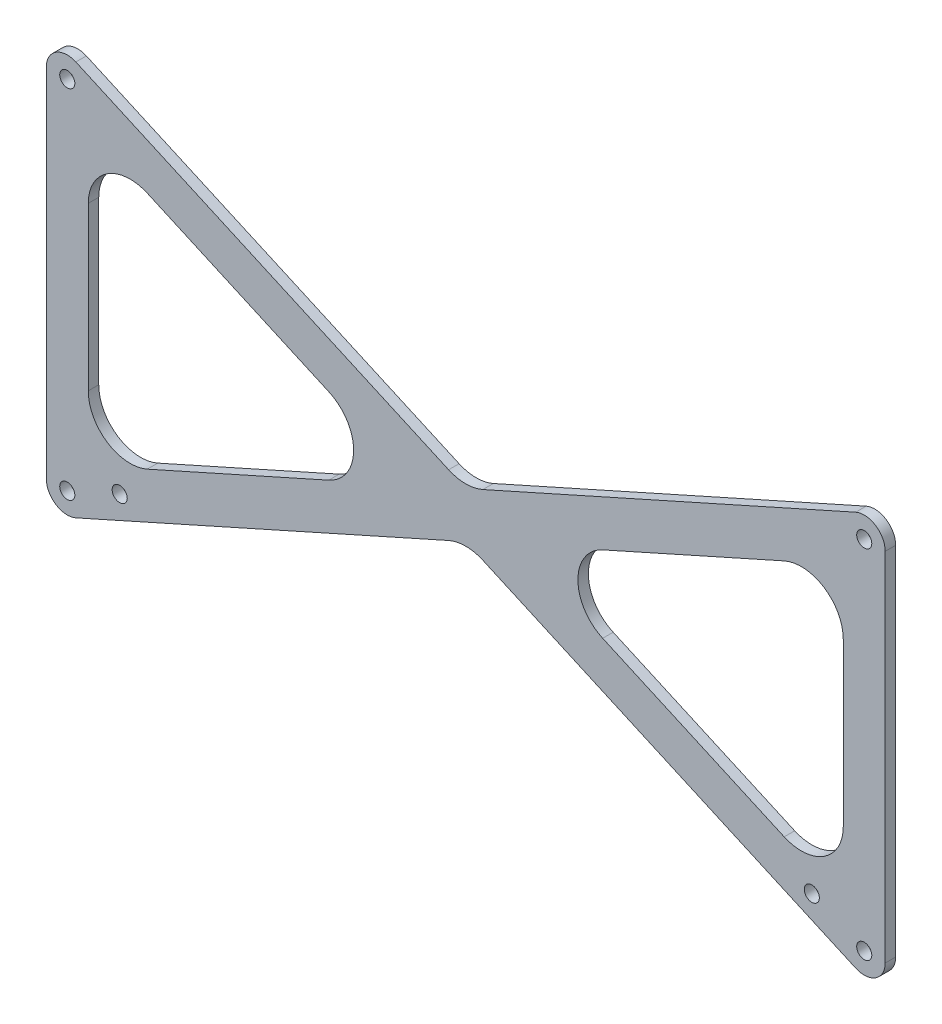
SolidWorks part; units mm, degrees
ref_plane "Front Plane" through (0, 0, 0) normal (0, 0, 1) x (1, 0, 0)
ref_plane "Top Plane" through (0, 0, 0) normal (0, 1, 0) x (1, 0, 0)
ref_plane "Right Plane" through (0, 0, 0) normal (1, 0, 0) x (0, 0, -1)
sketch "Sketch1" plane through (0, 0, 0) normal (0, 0, 1) x (1, 0, 0)
  line L0 (-120.65, -53.975) -> (120.65, 53.975) construction
  line L3 (-114.3, -44.1777) -> (-15.5498, 0)
  line L10 (-118.0569, -59.7714) -> (0, -6.9565)
  line L11 (-120.65, 53.975) -> (120.65, -53.975) construction
  line L12 (-118.0569, 59.7714) -> (0, 6.9565)
  line L13 (-114.3, 44.1777) -> (-15.5498, 0)
  line L14 (0, 6.9565) -> (118.0569, 59.7714)
  line L15 (0, -6.9565) -> (118.0569, -59.7714)
  line L16 (15.5498, 0) -> (114.3, 44.1777)
  line L17 (15.5498, 0) -> (114.3, -44.1777)
  line L18 (-127, 53.975) -> (-127, -53.975)
  line L19 (-114.3, 44.1777) -> (-114.3, -44.1777)
  line L20 (127, 53.975) -> (127, -53.975)
  line L21 (114.3, 44.1777) -> (114.3, -44.1777)
  arc A4 (-127, -53.975) -> (-118.0569, -59.7714) centre (-120.65, -53.975) ccw
  arc A5 (127, 53.975) -> (118.0569, 59.7714) centre (120.65, 53.975) ccw
  arc A6 (-118.0569, 59.7714) -> (-127, 53.975) centre (-120.65, 53.975) ccw
  arc A7 (118.0569, -59.7714) -> (127, -53.975) centre (120.65, -53.975) ccw
  point P2 (0, 0)
  point P9 (0, 0)
  point P13 (0, 0)
  point P26 (0, 0)
  dimension "D1" = 254
  dimension "D3" = 6.35
  dimension "D2" = 107.95
extrude "Boss-Extrude1" add sketch "Sketch1" along normal blind 3.175
sketch "Sketch2" plane through (0, 0, 3.175) normal (0, 0, 1) x (1, 0, 0)
  line L0 (127, -53.975) -> (127, 53.975) construction
  line L1 (-127, 53.975) -> (-127, -53.975) construction
  line L2 (-107.3681, -41.0766) -> (-102.1819, -52.6694) construction
  line L3 (-114.3, -44.1777) -> (-15.5498, 0) construction
  line L4 (-118.0569, -59.7714) -> (0, -6.9565) construction
  circle A0 centre (-120.65, 53.975) radius 2.286
  circle A1 centre (-120.65, -53.975) radius 2.286
  circle A2 centre (120.65, -53.975) radius 2.286
  circle A3 centre (120.65, 53.975) radius 2.286
  arc A4 (-118.0569, 59.7714) -> (-127, 53.975) centre (-120.65, 53.975) ccw construction
  arc A5 (-127, -53.975) -> (-118.0569, -59.7714) centre (-120.65, -53.975) ccw construction
  arc A6 (118.0569, -59.7714) -> (127, -53.975) centre (120.65, -53.975) ccw construction
  arc A7 (127, 53.975) -> (118.0569, 59.7714) centre (120.65, 53.975) ccw construction
  circle A8 centre (104.775, -46.873) radius 2.286
  circle A9 centre (-104.775, -46.873) radius 2.286
  point P24 (-104.775, -46.873)
  dimension "D1" = 4.572
  dimension "D2" = 22.225
  dimension "D3" = 22.225
extrude "Cut-Extrude1" cut sketch "Sketch2" against normal through all
fillet "Fillet1" radius 12.7 8 edges at (114.3, -44.1777, 1.5875) (114.3, 44.1777, 1.5875) (15.5498, 0, 1.5875) (-114.3, -44.1777, 1.5875) (-15.5498, 0, 1.5875) (-114.3, 44.1777, 1.5875) (0, 6.9565, 1.5875) (0, -6.9565, 1.5875)
